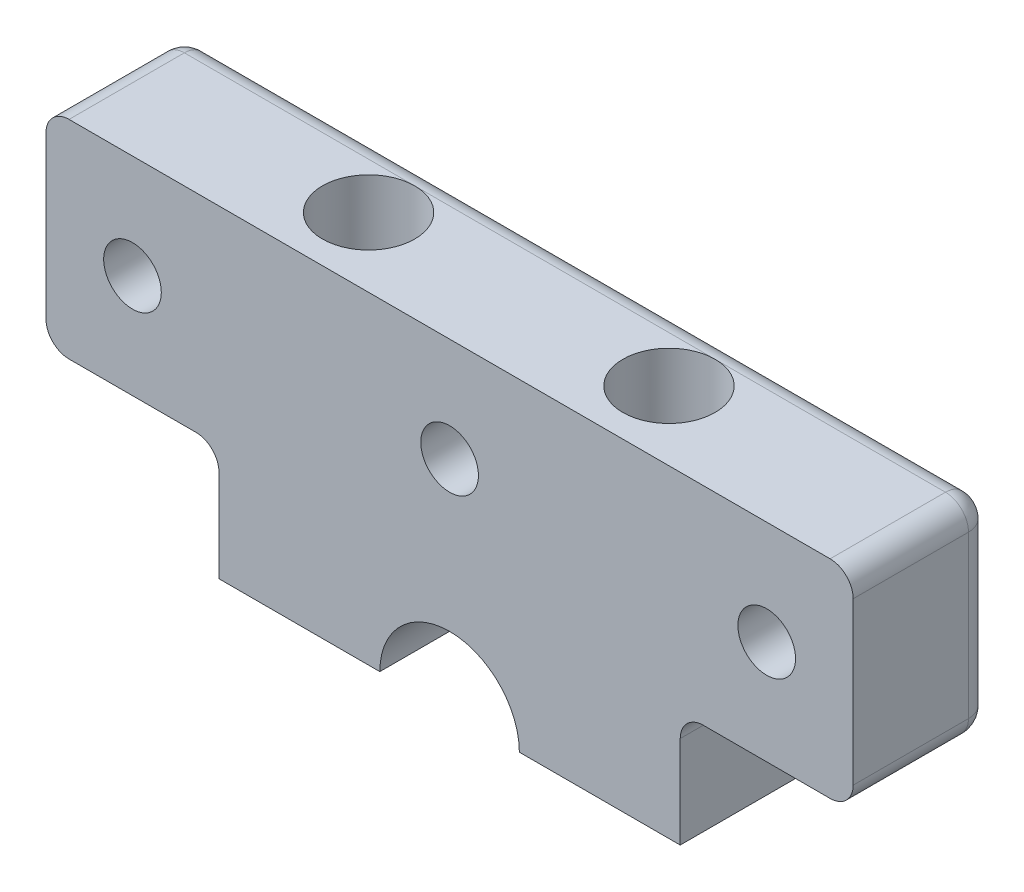
SolidWorks part; units mm, degrees
ref_plane "Plan de face" through (0, 0, 0) normal (0, 0, 1) x (1, 0, 0)
ref_plane "Plan de dessus" through (0, 0, 0) normal (0, 1, 0) x (1, 0, 0)
ref_plane "Plan de droite" through (0, 0, 0) normal (1, 0, 0) x (0, 0, -1)
sketch "Esquisse1" plane through (0, 0, 0) normal (0, 0, 1) x (1, 0, 0)
  line L1 (-16.8144, 9.7258) -> (23.1856, 9.7258)
  line L2 (-16.8144, 9.7258) -> (-16.8144, -8.2742)
  line L3 (-16.8144, -8.2742) -> (23.1856, -8.2742)
  line L4 (23.1856, 9.7258) -> (23.1856, -8.2742)
  dimension "D1" = 40
  dimension "D2" = 18
extrude "Boss.-Extru.1" add sketch "Esquisse1" along normal blind 12
sketch "Esquisse2" plane through (0, -8.2742, 0) normal (0, -1, 0) x (1, 0, 0)
  line L1 (23.1856, 0) -> (-16.8144, 0)
  line L2 (23.1856, 0) -> (23.1856, 12)
  line L3 (23.1856, 12) -> (-16.8144, 12)
  line L4 (-16.8144, 0) -> (-16.8144, 12)
extrude "Boss.-Extru.2" add sketch "Esquisse2" along normal blind 10
sketch "Esquisse3" plane through (0, 0, 12) normal (0, 0, 1) x (1, 0, 0)
  line L0 (3.1856, -18.2742) -> (3.1856, 9.7258) construction
  line L1 (23.1856, -18.2742) -> (-16.8144, -18.2742) construction
  line L2 (23.1856, 9.7258) -> (-16.8144, 9.7258) construction
  line L3 (-2.8644, -18.2742) -> (9.2356, -18.2742)
  arc A0 (-2.8644, -18.2742) -> (9.2356, -18.2742) centre (3.1856, -18.2742) cw
  dimension "D1" = 6.05
extrude "Enlèv. mat.-Extru.1" cut sketch "Esquisse3" against normal up to vertex (12 mm away) up to point (-16.8144, -18.2742, 0)
sketch "Esquisse4" plane through (0, -18.2742, 0) normal (0, -1, 0) x (1, 0, 0)
  line L0 (9.2356, 12) -> (23.1856, 0) construction
  line L1 (-2.8644, 0) -> (-16.8144, 12) construction
  circle A0 centre (-9.8394, 6) radius 2.5
  circle A1 centre (16.2106, 6) radius 2.5
  dimension "D1" = 5
  dimension "D2" = 5
extrude "Enlèv. mat.-Extru.2" cut sketch "Esquisse4" against normal up to vertex (28 mm away) up to point (23.1856, 9.7258, 12)
sketch "Esquisse5" plane through (0, 0, 12) normal (0, 0, 1) x (1, 0, 0)
  line L0 (23.1856, 0.7258) -> (-16.8144, 0.7258) construction
  line L1 (23.1856, -18.2742) -> (23.1856, 9.7258) construction
  line L2 (-16.8144, 9.7258) -> (-16.8144, -18.2742) construction
  line L3 (23.1856, 9.7258) -> (-16.8144, 9.7258) construction
  circle A1 centre (3.1856, 0.7258) radius 2.5
  dimension "D1" = 9
extrude "Enlèv. mat.-Extru.3" cut sketch "Esquisse5" against normal up to vertex (12 mm away) up to point (-16.8144, 9.7258, 0)
sketch "Esquisse6" plane through (0, 9.7258, 0) normal (0, 1, 0) x (1, 0, 0)
  circle A0 centre (16.2106, -6) radius 4
  circle A1 centre (-9.8394, -6) radius 4
  dimension "D1" = 8
extrude "Enlèv. mat.-Extru.5" cut sketch "Esquisse6" against normal blind 12
sketch "Esquisse7" plane through (-16.8144, 0, 0) normal (-1, 0, 0) x (0, 0, 1)
  line L0 (12, 9.7258) -> (12, -18.2742) construction
  line L1 (0, 9.7258) -> (12, 9.7258)
  line L2 (0, 9.7258) -> (0, -8.2742)
  line L3 (0, -8.2742) -> (12, -8.2742)
  line L4 (12, 9.7258) -> (12, -8.2742)
  dimension "D1" = 18
extrude "Boss.-Extru.3" add sketch "Esquisse7" along normal blind 15
sketch "Esquisse8" plane through (23.1856, 0, 0) normal (1, 0, 0) x (0, 0, -1)
  line L0 (-12, -18.2742) -> (-12, 9.7258) construction
  line L1 (0, 9.7258) -> (-12, 9.7258)
  line L2 (0, 9.7258) -> (0, -8.2742)
  line L3 (0, -8.2742) -> (-12, -8.2742)
  line L4 (-12, 9.7258) -> (-12, -8.2742)
  dimension "D1" = 18
extrude "Boss.-Extru.4" add sketch "Esquisse8" along normal blind 15
sketch "Esquisse9" plane through (0, 0, 12) normal (0, 0, 1) x (1, 0, 0)
  line L0 (30.6856, -8.2742) -> (30.6856, 9.7258) construction
  line L1 (38.1856, -8.2742) -> (23.1856, -8.2742) construction
  line L2 (38.1856, 9.7258) -> (-31.8144, 9.7258) construction
  line L3 (-24.3144, -8.2742) -> (-24.3144, 9.7258) construction
  line L4 (-31.8144, -8.2742) -> (-16.8144, -8.2742) construction
  circle A0 centre (-24.3144, 0.7258) radius 2.5
  circle A1 centre (30.6856, 0.7258) radius 2.5
  circle A2 centre (3.1856, 0.7258) radius 2.5 construction
extrude "Enlèv. mat.-Extru.6" cut sketch "Esquisse9" against normal up to vertex (12 mm away) up to point (-31.8144, 9.7258, 0)
fillet "Congé1" radius 2 13 edges at (-31.8144, 0.7258, 0) (38.1856, 0.7258, 0) (3.1856, 9.7258, 0) (23.1856, -8.2742, 6) (38.1856, -8.2742, 6) (38.1856, 9.7258, 6) (-31.8144, 9.7258, 6) (-31.8144, -8.2742, 6) (-16.8144, -8.2742, 6) (23.1856, -13.2742, 0) (-16.8144, -13.2742, 0) (30.6856, -8.2742, 0) (-24.3144, -8.2742, 0)
